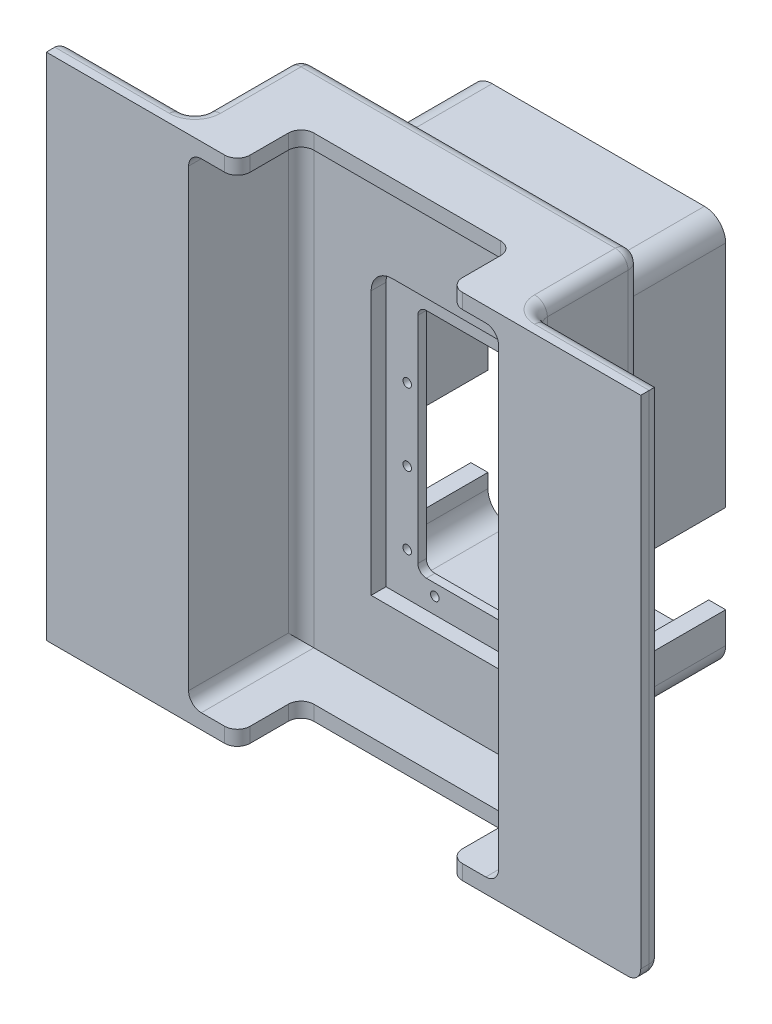
SolidWorks part; units mm, degrees
ref_plane "Front Plane" through (0, 0, 0) normal (0, 0, 1) x (1, 0, 0)
ref_plane "Top Plane" through (0, 0, 0) normal (0, 1, 0) x (1, 0, 0)
ref_plane "Right Plane" through (0, 0, 0) normal (1, 0, 0) x (0, 0, -1)
sketch "Sketch1" plane through (0, 0, 0) normal (0, 0, 1) x (1, 0, 0)
  line L0 (0, -32.545) -> (0, 18.055) construction
  line L1 (30, -53.3) -> (-30, -53.3)
  line L2 (30, -53.3) -> (30, 38.81)
  line L3 (30, 38.81) -> (-30, 38.81)
  line L4 (-30, -53.3) -> (-30, 38.81)
  line L5 (30, -53.3) -> (-30, 38.81) construction
  line L6 (30, 38.81) -> (-30, -53.3) construction
  point P0 (0, -7.245)
  point P13 (0, -7.245)
  dimension "D1" = 60
  dimension "D2" = 92.11
extrude "Boss-Extrude1" add sketch "Sketch1" against normal blind 30
sketch "Sketch2" plane through (0, 0, -30) normal (0, 0, -1) x (-1, 0, 0)
  line L8 (26, -49.3) -> (26, 34.81)
  line L9 (26, 34.81) -> (-26, 34.81)
  line L10 (-26, 34.81) -> (-26, -49.3)
  line L11 (-26, -49.3) -> (26, -49.3)
  line L12 (26, -49.3) -> (26, 34.81)
  line L13 (26, 34.81) -> (-26, 34.81)
  line L14 (-26, 34.81) -> (-26, -49.3)
  line L15 (-26, -49.3) -> (26, -49.3)
  dimension "D1" = 4
extrude "Cut-Extrude1" cut sketch "Sketch2" against normal offset from surface (28 mm away) 2 up to face at (0, -7.245, 0)
sketch "Sketch3" plane through (0, 0, -2) normal (0, 0, -1) x (-1, 0, 0)
  line L16 (26, 34.81) -> (-26, 34.81) construction
  line L17 (-12.5, 14.81) -> (12.5, 14.81)
  line L18 (-12.5, 14.81) -> (-12.5, -39.8)
  line L19 (-12.5, -39.8) -> (12.5, -39.8)
  line L20 (-26, 34.81) -> (-26, -49.3) construction
  line L21 (26, -49.3) -> (26, 34.81) construction
  line L22 (-26, -49.3) -> (26, -49.3) construction
  line L24 (-26, 34.81) -> (-26, -49.3)
  line L25 (26, -49.3) -> (26, 34.81)
  line L26 (26, 34.81) -> (-26, 34.81)
  line L27 (-26, -49.3) -> (26, -49.3)
  line L28 (12.5, 14.81) -> (12.5, -39.8)
  point P4 (0, -39.8)
  dimension "D2" = 9.5
  dimension "D3" = 13.5
  dimension "D1" = 20
extrude "Boss-Extrude2" add sketch "Sketch3" along normal blind 2
sketch "Sketch5" plane through (0, 0, -2) normal (0, 0, -1) x (-1, 0, 0)
  line L4 (12.5, 14.81) -> (-12.5, 14.81)
  line L5 (-12.5, 14.81) -> (-12.5, -39.8)
  line L6 (-12.5, -39.8) -> (12.5, -39.8)
  line L7 (12.5, -39.8) -> (12.5, 14.81)
  line L8 (12.5, 14.81) -> (-12.5, 14.81)
  line L9 (-12.5, 14.81) -> (-12.5, -39.8)
  line L10 (-12.5, -39.8) -> (12.5, -39.8)
  line L11 (12.5, -39.8) -> (12.5, 14.81)
  dimension "D1" = 0
extrude "Cut-Extrude2" cut sketch "Sketch5" against normal through all both and the other way through all
sketch "Sketch6" plane through (0, 0, -4) normal (0, 0, -1) x (-1, 0, 0)
  line L0 (-26, 34.81) -> (-26, -49.3) construction
  line L1 (-15, 20.81) -> (15, 20.81)
  line L2 (-20, 15.81) -> (-20, -46.3)
  line L3 (-20, -46.3) -> (20, -46.3)
  line L4 (20, 15.81) -> (20, -46.3)
  line L5 (26, -49.3) -> (26, 34.81) construction
  line L6 (-26, -49.3) -> (26, -49.3) construction
  line L8 (12.5, 14.81) -> (-12.5, 14.81) construction
  arc A0 (-15, 20.81) -> (-20, 15.81) centre (-15, 15.81) ccw
  arc A1 (15, 20.81) -> (20, 15.81) centre (15, 15.81) cw
  dimension "D5" = 5
  dimension "D1" = 6
  dimension "D2" = 6
  dimension "D3" = 3
  dimension "D4" = 6
extrude "Cut-Extrude3" cut sketch "Sketch6" against normal offset from surface (2 mm away) 2 up to face at (0, -12.495, 0)
sketch "Sketch7" plane through (0, 0, -30) normal (0, 0, -1) x (-1, 0, 0)
  line L1 (-34.6524, -20.1323) -> (34.8741, -20.1323)
  line L2 (-34.6524, -20.1323) -> (-34.6524, -40.9785)
  line L3 (-34.6524, -40.9785) -> (34.8741, -40.9785)
  line L4 (34.8741, -20.1323) -> (34.8741, -40.9785)
extrude "Cut-Extrude4" cut sketch "Sketch7" against normal up to surface (26 mm away) up to face at (0, -2.8815, -4)
sketch "Sketch14" plane through (0, 0, 0) normal (0, 0, 1) x (1, 0, 0)
  line L2 (40, 52.755) -> (40, -67.245)
  line L3 (40, -67.245) -> (-40, -67.245)
  line L4 (-40, 52.755) -> (-40, -67.245)
  line L5 (40, 52.755) -> (-40, -67.245) construction
  line L6 (40, -67.245) -> (-40, 52.755) construction
  line L14 (-40, 52.755) -> (40, 52.755)
  line L19 (30, -7.245) -> (38.1537, -7.245) construction
  line L20 (30, -53.3) -> (30, 38.81) construction
  line L21 (0, 0) -> (0, 105.51) construction
  point P8 (40, -7.245)
  point P12 (0, 52.755)
  dimension "D1" = 120
  dimension "D2" = 80
extrude "Boss-Extrude3" add sketch "Sketch14" along normal blind 30
sketch "Sketch15" plane through (0, 0, 30) normal (0, 0, 1) x (1, 0, 0)
  line L8 (-36.5, 49.255) -> (-36.5, -63.745)
  line L9 (-36.5, -63.745) -> (36.5, -63.745)
  line L10 (36.5, -63.745) -> (36.5, 49.255)
  line L11 (36.5, 49.255) -> (-36.5, 49.255)
  line L12 (-36.5, 49.255) -> (-36.5, -63.745)
  line L13 (-36.5, -63.745) -> (36.5, -63.745)
  line L14 (36.5, -63.745) -> (36.5, 49.255)
  line L15 (36.5, 49.255) -> (-36.5, 49.255)
  dimension "D1" = 3.5
extrude "Cut-Extrude5" cut sketch "Sketch15" against normal offset from surface (26.5 mm away) 3.5 up to face at (0, -7.245, 0)
fillet "Fillet1" radius 5 8 edges at (-26, -49.3, -17) (-30, -53.3, -15) (26, -49.3, -17) (30, -53.3, -15) (-26, 34.81, -17) (-30, 38.81, -15) (26, 34.81, -17) (30, 38.81, -15)
sketch "Sketch19" plane through (0, 0, 0) normal (0, 0, -1) x (-1, 0, 0)
  line L4 (-12.5, -39.8) -> (12.5, -39.8)
  line L5 (12.5, -39.8) -> (12.5, 14.81)
  line L6 (12.5, 14.81) -> (-12.5, 14.81)
  line L7 (-12.5, 14.81) -> (-12.5, -39.8)
  line L8 (-12.5, -39.8) -> (12.5, -39.8)
  line L9 (12.5, -39.8) -> (12.5, 14.81)
  line L10 (12.5, 14.81) -> (-12.5, 14.81)
  line L11 (-12.5, 14.81) -> (-12.5, -39.8)
  dimension "D1" = 0
extrude "Cut-Extrude8" cut sketch "Sketch19" against normal through all
sketch "Sketch21" plane through (0, 0, 3.5) normal (0, 0, 1) x (1, 0, 0)
  line L4 (-20, 15.81) -> (-20, -46.3)
  line L5 (15, 20.81) -> (-15, 20.81)
  line L6 (20, -46.3) -> (20, 15.81)
  line L7 (-20, -46.3) -> (20, -46.3)
  line L8 (-20, 15.81) -> (-20, -46.3)
  line L9 (15, 20.81) -> (-15, 20.81)
  line L10 (20, -46.3) -> (20, 15.81)
  line L11 (-20, -46.3) -> (20, -46.3)
  arc A2 (-15, 20.81) -> (-20, 15.81) centre (-15, 15.81) ccw
  arc A3 (20, 15.81) -> (15, 20.81) centre (15, 15.81) ccw
  arc A4 (-15, 20.81) -> (-20, 15.81) centre (-15, 15.81) ccw
  arc A5 (20, 15.81) -> (15, 20.81) centre (15, 15.81) ccw
  dimension "D1" = 0
extrude "Cut-Extrude9" cut sketch "Sketch21" against normal blind 3.5
fillet "Fillet3" radius 2 6 edges at (20, -46.3, -3) (12.5, -39.8, -1) (-20, -46.3, -3) (-12.5, -39.8, -1) (-12.5, 14.81, -1) (12.5, 14.81, -1)
sketch "Sketch27" plane through (0, 0, -2) normal (0, 0, -1) x (-1, 0, 0)
  point P0 (15, -2.2)
  point P1 (-15, -2.2)
  point P3 (-15, -19.2)
  point P5 (-15, -36.2)
  point P7 (-8.5, -42.5)
  point P9 (8.5, -42.5)
  point P11 (15, -36.2)
  point P13 (15, -19.2)
hole_wizard "Tap Drill for M2 Tap7" positions "3DSketch4" profile "Sketch28" hole size "M2" standard "ISO" end condition through all
sketch3d "3DSketch4"
  point P0 (15, -36.2, -2)
  point P3 (8.5, -42.5, -2)
  point P6 (-8.5, -42.5, -2)
  point P9 (-15, -36.2, -2)
  point P12 (-15, -19.2, -2)
  point P15 (-15, -2.2, -2)
  point P18 (15, -2.2, -2)
  point P21 (15, -19.2, -2)
sketch "Sketch28" plane through (15, -36.2, -2) normal (1, 0, 0) x (0, 1, 0)
  line L0 (0, 0) -> (0, 32)
  line L1 (0, 32) -> (1, 32)
  line L2 (1, 32) -> (1, 0)
  line L5 (1, 0) -> (0, 0)
  line L11 (0, -6.35) -> (0, 107.95) construction
  dimension "Thru Hole Dia." = 2
  dimension "Thru Hole Depth" = 32
sketch "Sketch31" plane through (40, 0, 0) normal (1, 0, 0) x (0, 0, -1)
  line L1 (-30, 52.755) -> (-25, 52.755)
  line L2 (-30, 52.755) -> (-30, -67.245)
  line L3 (-30, -67.245) -> (-25, -67.245)
  line L4 (-25, 52.755) -> (-25, -67.245)
  dimension "D1" = 5
extrude "Boss-Extrude4" add sketch "Sketch31" along normal blind 30
sketch "Sketch32" plane through (0, 52.755, 0) normal (0, 1, 0) x (1, 0, 0)
  line L0 (70, -30) -> (-40, -30) construction
  line L1 (-25, -45) -> (25, -45)
  line L2 (-25, -45) -> (-25, -15)
  line L3 (-25, -15) -> (25, -15)
  line L4 (25, -45) -> (25, -15)
  line L5 (-25, -45) -> (25, -15) construction
  line L6 (-25, -15) -> (25, -45) construction
  point P0 (0, -30)
  dimension "D1" = 50
  dimension "D2" = 30
extrude "Cut-Extrude10" cut sketch "Sketch32" against normal through all both and the other way through all
sketch "Sketch33" plane through (-40, 0, 0) normal (-1, 0, 0) x (0, 0, 1)
  line L4 (30, 52.755) -> (25, 52.755)
  line L5 (25, 52.755) -> (25, -67.245)
  line L6 (25, -67.245) -> (30, -67.245)
  line L7 (30, -67.245) -> (30, 52.755)
  line L8 (30, 52.755) -> (25, 52.755)
  line L9 (25, 52.755) -> (25, -67.245)
  line L10 (25, -67.245) -> (30, -67.245)
  line L11 (30, -67.245) -> (30, 52.755)
  dimension "D1" = 0
extrude "Boss-Extrude5" add sketch "Sketch33" along normal blind 30
fillet "Fillet4" radius 3 40 edges at (55, -67.245, 25) (55, 52.755, 25) (40, -7.245, 0) (0, 52.755, 0) (-40, -7.245, 0) (28.5355, -51.8355, 0) (0, -53.3, 0) (-28.5355, -51.8355, 0) (-30, -7.245, 0) (-28.5355, 37.3455, 0) (0, 38.81, 0) (28.5355, 37.3455, 0) (30, -7.245, 0) (70, -67.245, 27.5) (70, -7.245, 25) (40, -7.245, 25) (-40, -67.245, 12.5) (-40, 52.755, 12.5) (40, 52.755, 12.5) (40, -67.245, 12.5) (0, -67.245, 0) (-25, 51.005, 15) (25, 51.005, 15) (-25, -65.495, 15) (25, -65.495, 15) (-36.5, -7.245, 3.5) (-36.5, -63.745, 16.75) (-36.5, 49.255, 16.75) (0, 49.255, 3.5) (36.5, -7.245, 3.5) (36.5, -63.745, 16.75) (36.5, 49.255, 16.75) (-55, 52.755, 25) (-55, -67.245, 25) (-70, -7.245, 25) (-40, -7.245, 25) (-25, 51.005, 30) (25, 51.005, 30) (-25, -65.495, 30) (25, -65.495, 30)
